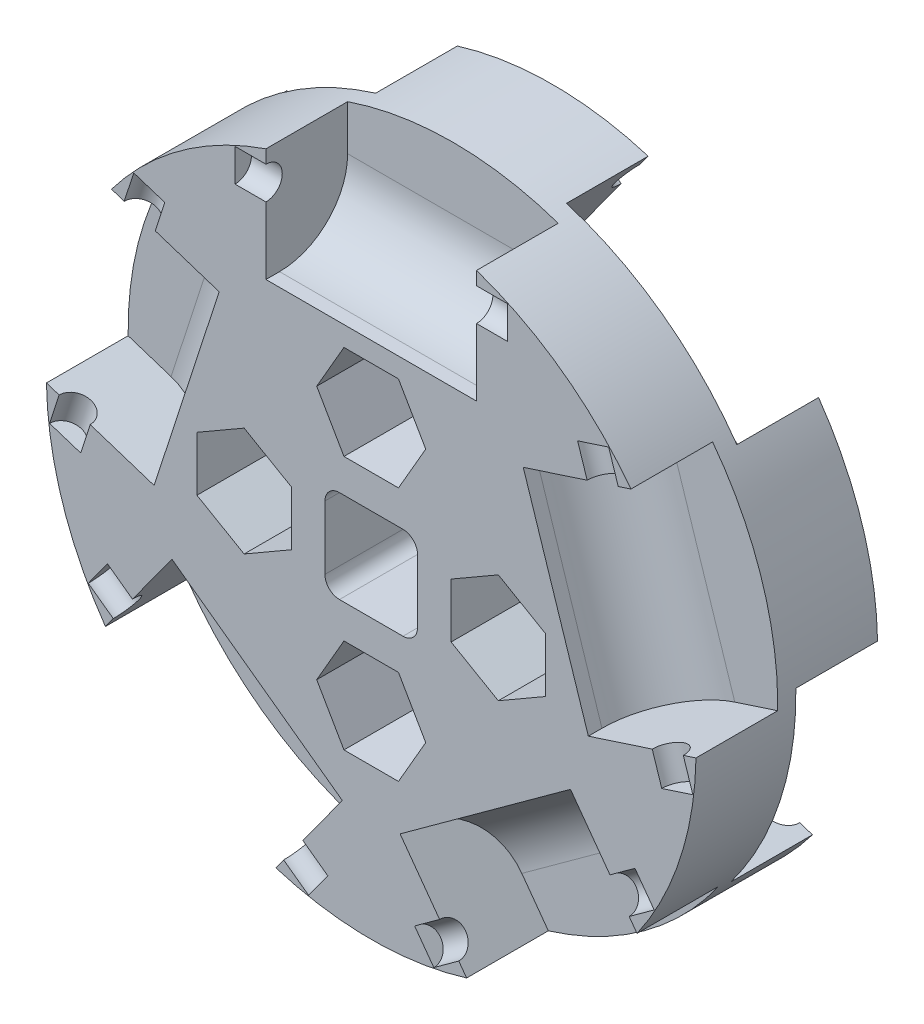
SolidWorks part; units mm, degrees
other "Markup1"
sketch "Sketch8" plane through (32.7336, 32.7336, 0) normal (0.5701, 0.1846, 0.8006) x (0.8043, 0.0736, -0.5897)
ref_plane "Front Plane" through (0, 0, 0) normal (0, 0, 1) x (1, 0, 0)
ref_plane "Top Plane" through (0, 0, 0) normal (0, 1, 0) x (1, 0, 0)
ref_plane "Right Plane" through (0, 0, 0) normal (1, 0, 0) x (0, 0, -1)
sketch "Sketch1" plane through (0, 0, 0) normal (0, 0, 1) x (1, 0, 0)
  circle A0 centre (0, 0) radius 22.7203
  dimension "D1" = 45.4406
extrude "Boss-Extrude2" add sketch "Sketch1" against normal blind 6.35
sketch "Sketch2" plane through (0, 0, 0) normal (0, 0, 1) x (1, 0, 0)
  line L1 (-12.7, 22.7203) -> (12.7, 22.7203) construction
  line L2 (-7.366, 23.9903) -> (7.366, 23.9903)
  line L3 (-7.366, 23.9903) -> (-7.366, 13.5763)
  line L4 (-7.366, 13.5763) -> (7.366, 13.5763)
  line L5 (7.366, 23.9903) -> (7.366, 13.5763)
  line L6 (-7.366, 23.9903) -> (7.366, 13.5763) construction
  line L7 (-7.366, 13.5763) -> (7.366, 23.9903) construction
  line L35 (0, 0) -> (0, 22.7203) construction
  circle A1 centre (0, 0) radius 22.7203 construction
  point P10 (0, 18.7833)
  circle M7 centre (0, 0) radius 22.7203
  dimension "D1" = 14.732
  dimension "D2" = 10.414
  dimension "D3" = 1.27
  dimension "D4" = 25.4
extrude "Cut-Extrude2" cut sketch "Sketch2" against normal blind 5.715 contours L5 L3 L4 M7
pattern_circular "CirPattern1" count 5 over 360 about axis through (0, 0, 0) along (0, 0, 1) of "Cut-Extrude2"
ref_plane "Plane1" through (0, 0, 0) normal (1, 0, 0) x (0, 0, -1)
sketch "Sketch4" plane through (0, 0, 0) normal (1, 0, 0) x (0, 0, -1)
  line L0 (5.715, 13.5763) -> (0, 13.5763) construction
  circle A0 centre (0, 19.4183) radius 1.143
  dimension "D1" = 2.286
  dimension "D2" = 5.842
extrude "Cut-Extrude4" cut sketch "Sketch4" against normal mid plane 19.05
pattern_circular "CirPattern2" count 5 over 360 about axis through (0, 0, 0) along (0, 0, 1) of "Cut-Extrude4"
sketch "Sketch5" plane through (0, 0, 0) normal (0, 0, 1) x (1, 0, 0)
  line L1 (-3.2385, -3.2385) -> (3.2385, -3.2385)
  line L2 (-3.2385, -3.2385) -> (-3.2385, 3.2385)
  line L3 (-3.2385, 3.2385) -> (3.2385, 3.2385)
  line L4 (3.2385, -3.2385) -> (3.2385, 3.2385)
  line L5 (-3.2385, -3.2385) -> (3.2385, 3.2385) construction
  line L6 (-3.2385, 3.2385) -> (3.2385, -3.2385) construction
  point P0 (0, 0)
  dimension "D1" = 6.477
extrude "Cut-Extrude5" cut sketch "Sketch5" against normal through all
sketch "Sketch6" plane through (0, 0, -6.35) normal (0, 0, -1) x (-1, 0, 0)
  line L0 (8.89, -3.8128) -> (12.192, -1.9064)
  line L1 (12.192, -1.9064) -> (12.192, 1.9064)
  line L2 (12.192, 1.9064) -> (8.89, 3.8128)
  line L3 (3.8128, 8.89) -> (1.9064, 12.192)
  line L4 (1.9064, 12.192) -> (-1.9064, 12.192)
  line L5 (-1.9064, 12.192) -> (-3.8128, 8.89)
  line L6 (-3.8128, 8.89) -> (-1.9064, 5.588)
  line L7 (-1.9064, 5.588) -> (1.9064, 5.588)
  line L8 (1.9064, 5.588) -> (3.8128, 8.89)
  line L9 (8.89, 3.8128) -> (5.588, 1.9064)
  line L10 (5.588, 1.9064) -> (5.588, -1.9064)
  line L11 (5.588, -1.9064) -> (8.89, -3.8128)
  line L12 (-3.8128, -8.89) -> (-1.9064, -12.192)
  line L13 (-1.9064, -12.192) -> (1.9064, -12.192)
  line L14 (1.9064, -12.192) -> (3.8128, -8.89)
  line L15 (3.8128, -8.89) -> (1.9064, -5.588)
  line L16 (1.9064, -5.588) -> (-1.9064, -5.588)
  line L17 (-1.9064, -5.588) -> (-3.8128, -8.89)
  line L18 (-8.89, 3.8128) -> (-12.192, 1.9064)
  line L19 (-12.192, 1.9064) -> (-12.192, -1.9064)
  line L20 (-12.192, -1.9064) -> (-8.89, -3.8128)
  line L21 (-8.89, -3.8128) -> (-5.588, -1.9064)
  line L22 (-5.588, -1.9064) -> (-5.588, 1.9064)
  line L23 (-5.588, 1.9064) -> (-8.89, 3.8128)
  circle A4 centre (0, 8.89) radius 3.302 construction
  circle A5 centre (8.89, 0) radius 3.302 construction
  circle A6 centre (0, -8.89) radius 3.302 construction
  circle A7 centre (-8.89, 0) radius 3.302 construction
  dimension "D3" = 4
  dimension "D1" = 6.604
  dimension "D2" = 8.89
extrude "Cut-Extrude7" cut sketch "Sketch6" against normal through all
sketch "Sketch9" plane through (0, 0, -6.35) normal (0, 0, -1) x (-1, 0, 0)
  line L0 (3.2385, -3.2385) -> (-3.2385, -3.2385) construction
  line L1 (-3.2385, 3.2385) -> (3.2385, 3.2385)
  line L2 (-3.2385, 3.2385) -> (-3.2385, -3.2385)
  line L3 (-3.2385, -3.2385) -> (3.2385, -3.2385)
  line L4 (3.2385, 3.2385) -> (3.2385, -3.2385)
  line L5 (-3.2385, 3.2385) -> (3.2385, -3.2385) construction
  line L6 (-3.2385, -3.2385) -> (3.2385, 3.2385) construction
  line L7 (8.89, -3.8128) -> (12.192, -1.9064)
  line L8 (3.8128, 8.89) -> (1.9064, 12.192)
  line L9 (1.9064, 12.192) -> (-1.9064, 12.192)
  line L10 (-1.9064, 12.192) -> (-3.8128, 8.89)
  line L11 (-3.8128, 8.89) -> (-1.9064, 5.588)
  line L12 (-1.9064, 5.588) -> (1.9064, 5.588)
  line L13 (1.9064, 5.588) -> (3.8128, 8.89)
  line L14 (12.192, -1.9064) -> (12.192, 1.9064)
  line L15 (12.192, 1.9064) -> (8.89, 3.8128)
  line L16 (8.89, 3.8128) -> (5.588, 1.9064)
  line L17 (5.588, 1.9064) -> (5.588, -1.9064)
  line L18 (5.588, -1.9064) -> (8.89, -3.8128)
  line L19 (-3.8128, -8.89) -> (-1.9064, -12.192)
  line L20 (-1.9064, -12.192) -> (1.9064, -12.192)
  line L21 (1.9064, -12.192) -> (3.8128, -8.89)
  line L22 (3.8128, -8.89) -> (1.9064, -5.588)
  line L23 (1.9064, -5.588) -> (-1.9064, -5.588)
  line L24 (-1.9064, -5.588) -> (-3.8128, -8.89)
  line L25 (-8.89, 3.8128) -> (-12.192, 1.9064)
  line L26 (-12.192, 1.9064) -> (-12.192, -1.9064)
  line L27 (-12.192, -1.9064) -> (-8.89, -3.8128)
  line L28 (-8.89, -3.8128) -> (-5.588, -1.9064)
  line L29 (-5.588, -1.9064) -> (-5.588, 1.9064)
  line L30 (-5.588, 1.9064) -> (-8.89, 3.8128)
  line L31 (-1.9064, 5.588) -> (1.9064, 5.588) construction
  circle A0 centre (0, 0) radius 22.7203
  circle A5 centre (0, 8.89) radius 3.302 construction
  circle A6 centre (8.89, 0) radius 3.302 construction
  circle A7 centre (0, -8.89) radius 3.302 construction
  circle A8 centre (-8.89, 0) radius 3.302 construction
  circle A9 centre (0, 0) radius 22.7203 construction
  dimension "D3" = 4
extrude "Boss-Extrude3" add sketch "Sketch9" along normal blind 6.35
sketch "Sketch10" plane through (0, 0, -12.7) normal (0, 0, -1) x (-1, 0, 0)
  line L0 (-26.0547, 18.3811) -> (-0.6547, 18.3811) construction
  line L1 (-2.0207, 15.3131) -> (-13.9392, 6.6538)
  line L2 (-2.0207, 15.3131) -> (-8.1419, 23.7382)
  line L3 (-8.1419, 23.7382) -> (-20.0604, 15.0789)
  line L4 (-13.9392, 6.6538) -> (-20.0604, 15.0789)
  line L5 (-2.0207, 15.3131) -> (-20.0604, 15.0789) construction
  line L6 (-8.1419, 23.7382) -> (-13.9392, 6.6538) construction
  line L7 (0, 0) -> (-13.3547, 18.3811) construction
  line L8 (0, 0) -> (0, 40.3277) construction
  circle A2 centre (0, 0) radius 22.7203 construction
  point P8 (-11.0405, 15.196)
  dimension "D1" = 1.27
  dimension "D2" = 14.732
  dimension "D3" = 10.414
  dimension "D4" = 25.4
  dimension "D5" = 36
extrude "Cut-Extrude8" cut sketch "Sketch10" against normal blind 5.715
pattern_circular "CirPattern3" count 5 over 360 about axis through (0, 0, 0) along (0, 0, 1) of "Cut-Extrude8"
ref_plane "Plane2" through (0, 0, 0) normal (-0.809, 0.5878, 0) x (0, 0, -1)
sketch "Sketch11" plane through (0, 0, 0) normal (-0.809, 0.5878, 0) x (0, 0, -1)
  line L5 (6.985, -13.5763) -> (12.7, -13.5763) construction
  line L6 (12.7, -21.4931) -> (12.7, -13.6472) construction
  circle A0 centre (12.7, -19.4183) radius 1.143
  dimension "D1" = 2.286
  dimension "D2" = 5.842
extrude "Cut-Extrude9" cut sketch "Sketch11" against normal mid plane 19.05
pattern_circular "CirPattern4" count 5 over 360 about axis through (0, 0, 0) along (0, 0, 1) of "Cut-Extrude9"
fillet "Fillet1" radius 4.7625 10 edges at (0, 13.5763, -5.715) (7.9799, 10.9835, -6.985) (12.9118, -4.1953, -6.985) (0, -13.5763, -6.985) (-12.9118, -4.1953, -6.985) (7.9799, -10.9835, -5.715) (-7.9799, 10.9835, -6.985) (-7.9799, -10.9835, -5.715) (12.9118, 4.1953, -5.715) (-12.9118, 4.1953, -5.715)
fillet "Fillet2" radius 1.016 4 edges at (3.2385, -3.2385, -6.35) (3.2385, 3.2385, -6.35) (-3.2385, 3.2385, -6.35) (-3.2385, -3.2385, -6.35)
